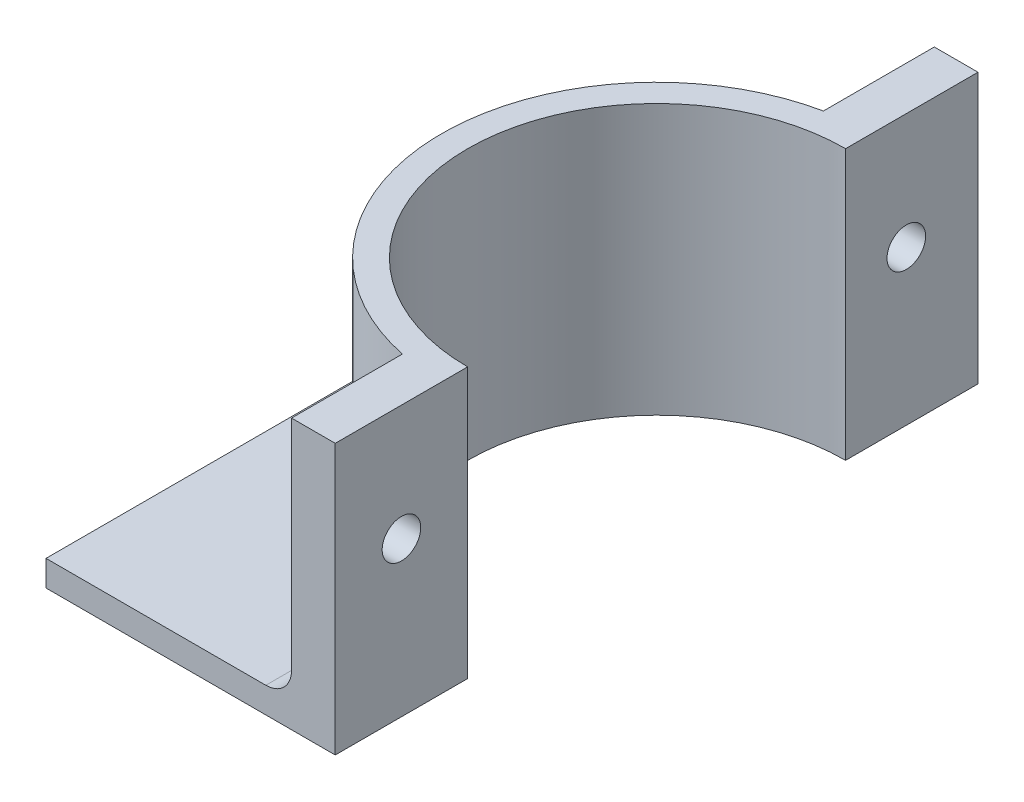
SolidWorks part; units mm, degrees
ref_plane "Front Plane" through (0, 0, 0) normal (0, 0, 1) x (1, 0, 0)
ref_plane "Top Plane" through (0, 0, 0) normal (0, 1, 0) x (1, 0, 0)
ref_plane "Right Plane" through (0, 0, 0) normal (1, 0, 0) x (0, 0, -1)
sketch "Sketch3" plane through (0, 0, 0) normal (0, 1, 0) x (1, 0, 0)
  line L0 (0, 0) -> (0, 63.5)
  line L1 (0, 63.5) -> (57.15, 63.5)
  line L2 (57.15, 63.5) -> (57.15, 0)
  line L3 (57.15, 0) -> (0, 0)
  line L4 (28.575, 63.5) -> (28.575, 0)
  line L7 (24.257, 63.5) -> (24.257, 52.5466)
  line L8 (32.893, 63.5) -> (32.893, 52.5466)
  line L9 (24.257, 0) -> (24.257, 10.9534)
  line L10 (32.893, 0) -> (32.893, 10.9534)
  circle A0 centre (28.575, 31.75) radius 18.669
  arc A2 (24.257, 52.5466) -> (24.257, 10.9534) centre (28.575, 31.75) ccw
  arc A3 (32.893, 10.9534) -> (32.893, 52.5466) centre (28.575, 31.75) ccw
  point P9 (0, 0)
  point P10 (0, 0)
sketch "Sketch5" plane through (0, 0, 0) normal (1, 0, 0) x (0, 0, -1)
  circle A0 centre (6.5405, 15.24) radius 1.905
  circle A1 centre (56.4176, 15.24) radius 1.905
extrude "Boss-Extrude14" add sketch "Sketch3" along normal blind 2.54 contours A2 L7 L1 L0 L3 L9 region at (0.6798, 0, -31.75)
extrude "Boss-Extrude15" add sketch "Sketch3<18>" along normal blind 26.67 contours L7 A2 L9 L3 L4 A0 L1 region at (24.9266, 0, -5.4767)
sketch "Sketch3<18>" plane through (0, 0, 0) normal (0, 1, 0) x (1, 0, 0) same geometry as "Sketch3"
extrude "Cut-Extrude12" cut sketch "Sketch5" along normal through all
fillet "Fillet3" radius 2.54 3 edges at (24.257, 2.54, -58.0233) (7.3348, 2.54, -31.75) (24.257, 2.54, -5.4767)
